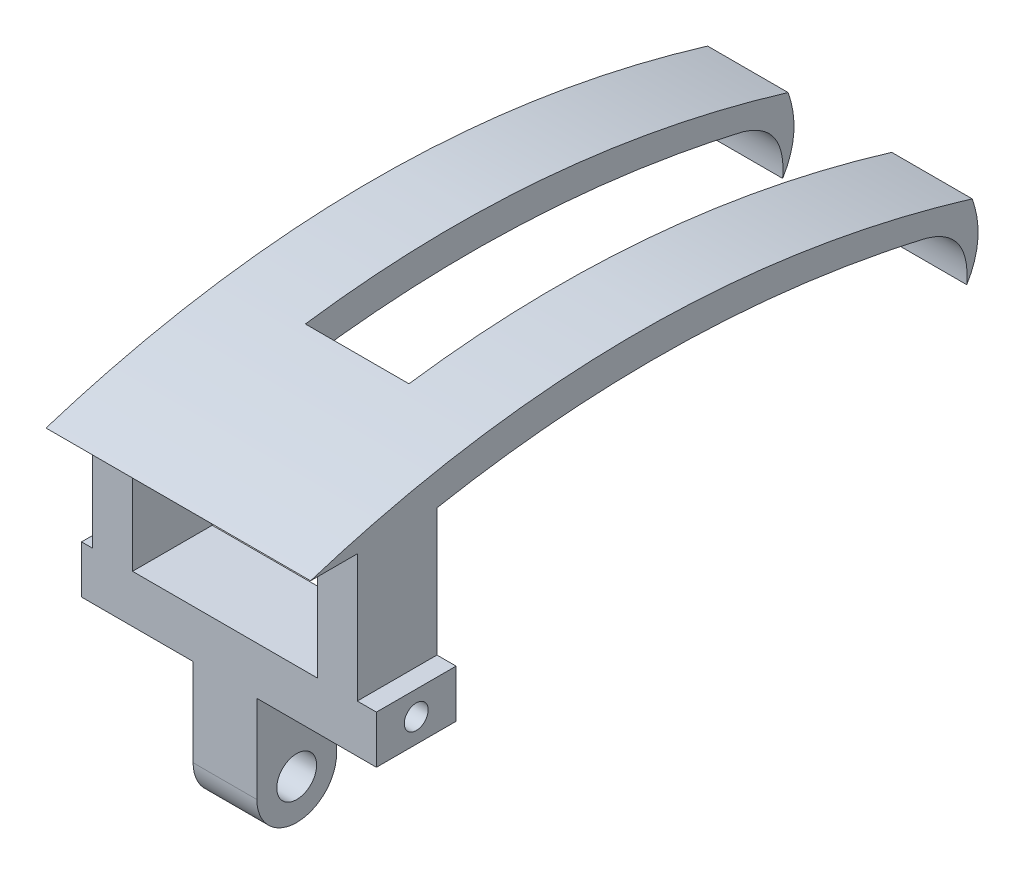
SolidWorks part; units mm, degrees
ref_plane "前视基准面" through (0, 0, 0) normal (0, 0, 1) x (1, 0, 0)
ref_plane "上视基准面" through (0, 0, 0) normal (0, 1, 0) x (1, 0, 0)
ref_plane "右视基准面" through (0, 0, 0) normal (1, 0, 0) x (0, 0, -1)
sketch "草图1" plane through (0, 0, 0) normal (0, 1, 0) x (1, 0, 0)
  line L1 (0, 0) -> (180, 0)
  line L2 (0, 0) -> (0, -50)
  line L3 (0, -50) -> (180, -50)
  line L4 (180, 0) -> (180, -50)
  dimension "D1" = 180
  dimension "D2" = 50
extrude "凸台-拉伸1" add sketch "草图1" along normal blind 30 contours L2 L1 L4 L3
sketch "草图2" plane through (0, 0, 0) normal (0, -1, 0) x (1, 0, 0)
  line L0 (90, 50) -> (90, 0) construction
  line L1 (0, 50) -> (180, 50) construction
  line L2 (0, 0) -> (180, 0) construction
  line L4 (70, 0) -> (110, 0)
  line L5 (70, 0) -> (70, 50)
  line L6 (70, 50) -> (110, 50)
  line L7 (110, 0) -> (110, 50)
  line L8 (70, 0) -> (110, 50) construction
  line L9 (70, 50) -> (110, 0) construction
  point P4 (90, 25)
  dimension "D1" = 40
extrude "凸台-拉伸2" add sketch "草图2" along normal blind 80
fillet "圆角1" radius 25 2 edges at (90, -80, 50) (90, -80, 0)
sketch "草图3" plane through (110, 0, 0) normal (1, 0, 0) x (0, 0, -1)
  line L3 (-50, 0) -> (-50, -55)
  line L4 (0, -55) -> (0, 0)
  line L5 (0, 0) -> (-50, 0)
  line L6 (-50, 0) -> (-50, -55) construction
  line L7 (0, -55) -> (0, 0) construction
  line L8 (0, 0) -> (-50, 0) construction
  circle A0 centre (-25, -55) radius 12.5
  arc A2 (-50, -55) -> (-25, -80) centre (-25, -55) ccw
  arc A3 (-25, -80) -> (0, -55) centre (-25, -55) ccw
  arc A4 (-50, -55) -> (-25, -80) centre (-25, -55) ccw construction
  arc A5 (-25, -80) -> (0, -55) centre (-25, -55) ccw construction
  dimension "D2" = 25
  dimension "D1" = 0
extrude "切除-拉伸2" cut sketch "草图3" against normal through all
sketch "草图4" plane through (0, 0, 50) normal (0, 0, 1) x (1, 0, 0)
  line L2 (90, 30) -> (90, -18.483) construction
  line L3 (0, 30) -> (180, 30) construction
  line L4 (0, 0) -> (70, 0) construction
  line L5 (7, 30) -> (32, 30)
  line L6 (7, 30) -> (7, 0)
  line L7 (7, 0) -> (32, 0)
  line L8 (32, 30) -> (32, 0)
  line L9 (0, 30) -> (0, 0) construction
  line L10 (173, 0) -> (148, 0)
  line L11 (148, 30) -> (148, 0)
  line L12 (173, 30) -> (148, 30)
  line L13 (173, 30) -> (173, 0)
  dimension "D1" = 7
  dimension "D2" = 25
sketch "草图7" plane through (0, 30, 0) normal (0, 1, 0) x (1, 0, 0)
  line L0 (7, -50) -> (32, -50) construction
  line L1 (7, -50) -> (32, -50)
  line L2 (7, -50) -> (7, 0)
  line L3 (7, 0) -> (32, 0)
  line L4 (32, -50) -> (32, 0)
  line L5 (0, 0) -> (180, 0) construction
  line L6 (173, -50) -> (148, -50) construction
  line L7 (148, -50) -> (173, -50)
  line L8 (148, -50) -> (148, 0)
  line L9 (148, 0) -> (173, 0)
  line L10 (173, -50) -> (173, 0)
  line L11 (0, -50) -> (180, -50) construction
extrude "凸台-拉伸5" add sketch "草图7" along normal blind 80 contours L2 L1 L4 L3 | L8 L7 L10 L9
sketch "草图8" plane through (173, 0, 0) normal (1, 0, 0) x (0, 0, -1)
  line L0 (0, 110) -> (-79.2937, 110)
  line L4 (-50, 30) -> (0, 30)
  line L5 (0, 30) -> (0, 110)
  line L6 (0, 110) -> (-50, 110)
  line L7 (-50, 110) -> (-50, 30)
  line L8 (-50, 30) -> (0, 30) construction
  line L9 (0, 30) -> (0, 110) construction
  line L10 (0, 110) -> (-50, 110) construction
  line L11 (-50, 110) -> (-50, 30) construction
  spline S0 degree 2 poles (-79.2937, 110) (123.3227, 174.3751) (335.8084, 110) knots 0 0 0 1 1 1
  spline S1 degree 2 poles (335.8084, 110) (344.6552, 85.0089) (332.3867, 65.0246) knots 0 0 0 1 1 1
  spline S2 degree 2 poles (332.3867, 65.0246) (334.882, 94.7931) (307.3283, 102.8847) knots 0 0 0 1 1 1
  spline S3 degree 2 poles (307.3283, 102.8847) (153.5711, 138.7084) (0, 110) knots 0 0 0 1 1 1
  dimension "D1" = 0
extrude "凸台-拉伸6" add sketch "草图8" against normal up to surface (166 mm away) up to face at (7, 70, 25)
sketch "草图9" plane through (0, 30, 0) normal (0, 1, 0) x (1, 0, 0)
  line L0 (90, -30.1798) -> (90, 231.3313) construction
  line L1 (57.5, 363.3701) -> (57.5, 32.9289)
  line L2 (57.5, 363.3701) -> (122.5, 363.3701)
  line L3 (57.5, 32.9289) -> (122.5, 32.9289)
  line L4 (32, -50) -> (148, -50)
  line L5 (148, -50) -> (148, 0)
  line L6 (148, 0) -> (32, 0)
  line L7 (32, 0) -> (32, -50)
  line L8 (32, -50) -> (148, -50) construction
  line L9 (148, -50) -> (148, 0) construction
  line L10 (148, 0) -> (32, 0) construction
  line L11 (32, 0) -> (32, -50) construction
  line L12 (122.5, 363.3701) -> (122.5, 32.9289)
  line L13 (57.5, 363.3701) -> (122.5, 32.9289) construction
  line L14 (57.5, 32.9289) -> (122.5, 363.3701) construction
  point P7 (90, 198.1495)
  point P14 (90, 0)
  dimension "D2" = 65
  dimension "D1" = 0
extrude "切除-拉伸4" cut sketch "草图9" along normal through all
sketch "草图10" plane through (180, 0, 0) normal (1, 0, 0) x (0, 0, -1)
  line L4 (-50, 0) -> (0, 0)
  line L5 (0, 0) -> (0, 30)
  line L6 (0, 30) -> (-50, 30)
  line L7 (-50, 30) -> (-50, 0)
  line L8 (-50, 0) -> (0, 0)
  line L9 (0, 0) -> (0, 30)
  line L10 (0, 30) -> (-50, 30)
  line L11 (-50, 30) -> (-50, 0)
  dimension "D1" = 0
extrude "凸台-拉伸7" add sketch "草图10" along normal blind 10
sketch "草图11" plane through (190, 0, 0) normal (1, 0, 0) x (0, 0, -1)
  line L4 (-50, 30) -> (-50, 0)
  line L5 (-50, 0) -> (0, 0)
  line L6 (0, 0) -> (0, 30)
  line L7 (0, 30) -> (-50, 30)
  line L8 (-50, 30) -> (-50, 0)
  line L9 (-50, 0) -> (0, 0)
  line L10 (0, 0) -> (0, 30)
  line L11 (0, 30) -> (-50, 30)
  dimension "D1" = 0
extrude "切除-拉伸5" cut sketch "草图11" against normal blind 5
sketch "草图12" plane through (185, 0, 0) normal (1, 0, 0) x (0, 0, -1)
  line L0 (0, 15) -> (-83.9093, 15) construction
  line L1 (0, 0) -> (0, 30) construction
  line L2 (-25, 30) -> (-25, 15) construction
  line L3 (-50, 30) -> (0, 30) construction
  circle A0 centre (-25, 15) radius 7.5
  dimension "D1" = 15
extrude "切除-拉伸6" cut sketch "草图12" against normal through all
